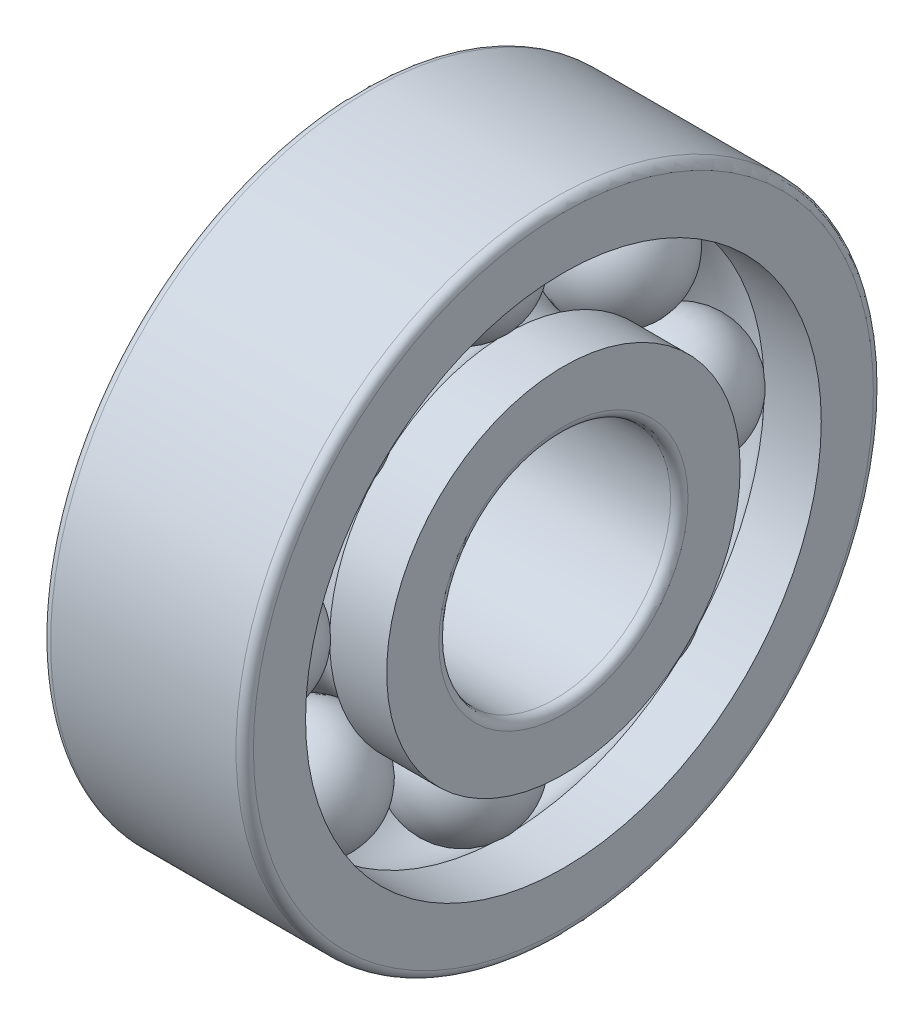
SolidWorks part; units mm, degrees
ref_plane "Plane1" through (0, 0, 0) normal (0, 0, 1) x (1, 0, 0)
ref_plane "Plane2" through (0, 0, 0) normal (0, 1, 0) x (1, 0, 0)
ref_plane "Plane3" through (0, 0, 0) normal (1, 0, 0) x (0, 0, -1)
sketch "Clipboard" plane through (0, 0, 0) normal (0, 0, 1) x (1, 0, 0)
  line L0 (-10, 0) -> (10, 0) construction
  line L1 (0, 0) -> (22.1431, -3.112)
  line L2 (0, 0) -> (7.427, 1.0438)
  line L3 (0, 0) -> (22.1431, -3.112)
  line L4 (0, 0) -> (-22.3573, -0.3902)
  dimension "BallCLRad" = 7.5
sketch "CagSpiSke" plane through (0, 0, 0) normal (0, 0, 1) x (1, 0, 0)
  line L0 (0.21, 7.15) -> (0.21, 7.85)
  line L1 (0.21, 7.85) -> (-0.21, 7.85)
  line L2 (-0.21, 7.85) -> (-0.21, 7.15)
  line L3 (-0.21, 7.15) -> (0.21, 7.15)
  line L4 (-20.6375, 0) -> (20.6375, 0) construction
  line L5 (0, 0) -> (0, 23.7692) construction
  dimension "OD" = 15.7
  dimension "ID" = 14.3
revolve "CageSpine" add sketch "CagSpiSke" angle 0.001 about L4 reverse direction yes
ref_axis "Axis1" through (-50, 0, 0) along (1, 0, 0)
sketch "CagBalSke" plane through (0, 0, 0) normal (0, 0, 1) x (1, 0, 0)
  line L0 (-2.31, 7.5) -> (2.31, 7.5)
  line L1 (-1.905, 7.5) -> (1.905, 7.5) construction
  line L2 (-10, 0) -> (10, 0) construction
  line L3 (0, 0) -> (0, 24) construction
  arc A0 (2.31, 7.5) -> (-2.31, 7.5) centre (0, 7.5) cw
  dimension "BallCLRad" = 7.5
revolve "CageBall" [suppressed] add sketch "CagBalSke" angle 360 about L1 reverse direction yes
pattern_circular "CageBalls" [suppressed] count 8 every 45 about axis through (-50, 0, 0) along (1, 0, 0)
sketch "CagTrmODSke" plane through (0, 0, 0) normal (0, 0, 1) x (1, 0, 0)
  line L0 (2.311, 7.85) -> (2.311, 9.811)
  line L1 (2.311, 9.811) -> (-2.311, 9.811)
  line L2 (-2.311, 9.811) -> (-2.311, 7.85)
  line L3 (-2.311, 7.85) -> (2.311, 7.85)
  line L4 (-20.6375, 0) -> (20.6375, 0) construction
  line L5 (0, 0) -> (0, 25) construction
  dimension "Width" = 4.622
  dimension "ID" = 15.7
  dimension "OD" = 19.622
revolve "CageTrimOD" [suppressed] cut sketch "CagTrmODSke" angle 360 about L4 reverse direction yes
sketch "CagTrmIDSke" plane through (0, 0, 0) normal (0, 0, 1) x (1, 0, 0)
  line L0 (2.311, 5.191) -> (2.311, 7.15)
  line L1 (2.311, 7.15) -> (-2.311, 7.15)
  line L2 (-2.311, 7.15) -> (-2.311, 5.191)
  line L3 (-2.311, 5.191) -> (2.311, 5.191)
  line L4 (-20.6375, 0) -> (20.6375, 0) construction
  line L5 (0, 0) -> (0, 25) construction
  dimension "Width" = 4.622
  dimension "ID" = 10.382
  dimension "OD" = 14.3
revolve "CageTrimID" [suppressed] cut sketch "CagTrmIDSke" angle 360 about L4 reverse direction yes
sketch "BalSimSke" plane through (0, 0, 0) normal (0, 0, 1) x (1, 0, 0)
  line L0 (-10, 0) -> (10, 0) construction
  line L1 (-10, 7.5) -> (10, 7.5) construction
  line L2 (0, 0) -> (0, 23) construction
  circle A0 centre (0, 7.5) radius 2.1
  dimension "BallCLRad" = 7.5
  dimension "Ball_diameter" = 4.2
revolve "BallsSimplified" [suppressed] add sketch "BalSimSke" angle 360 about L0
sketch "BalDetSke" plane through (0, 0, 0) normal (0, 0, 1) x (1, 0, 0)
  line L0 (-2.1, 7.5) -> (2.1, 7.5)
  line L1 (-1.905, 7.5) -> (1.905, 7.5) construction
  line L2 (0, 0) -> (0, 25) construction
  arc A0 (2.1, 7.5) -> (-2.1, 7.5) centre (0, 7.5) cw
  dimension "BallCLRad" = 7.5
  dimension "Ball_diameter" = 4.2
revolve "BallDetailed" add sketch "BalDetSke" angle 360 about L1 reverse direction yes
sketch "InnRacSke" plane through (0, 0, 0) normal (0, 0, 1) x (1, 0, 0)
  line L0 (-1.5315, 6.1) -> (-3.5, 6.1)
  line L1 (-3.5, 6.1) -> (-3.5, 4.3)
  line L2 (-3.2, 4) -> (3.2, 4)
  line L3 (3.5, 4.3) -> (3.5, 6.1)
  line L4 (3.5, 6.1) -> (1.5315, 6.1)
  line L5 (-20.6375, 0) -> (20.6375, 0) construction
  line L6 (0, 0) -> (0, 30) construction
  arc A0 (-3.5, 4.3) -> (-3.2, 4) centre (-3.2, 4.3) ccw
  arc A1 (3.2, 4) -> (3.5, 4.3) centre (3.2, 4.3) ccw
  arc A2 (1.5315, 6.1) -> (-1.5315, 6.1) centre (0, 7.5) cw
  dimension "BallCLRad" = 7.5
  dimension "Fillet_radius" = 0.3
  dimension "Ball_diameter" = 4.15
  dimension "ID" = 8
  dimension "OD" = 12.2
  dimension "Width" = 7
revolve "InnerRace" add sketch "InnRacSke" angle 360 about L5 reverse direction yes
sketch "OutRacSke" plane through (0, 0, 0) normal (0, 0, 1) x (1, 0, 0)
  line L0 (-1.5315, 8.9) -> (-3.5, 8.9)
  line L1 (-3.5, 8.9) -> (-3.5, 10.7)
  line L2 (-3.2, 11) -> (3.2, 11)
  line L3 (3.5, 10.7) -> (3.5, 8.9)
  line L4 (3.5, 8.9) -> (1.5315, 8.9)
  line L5 (-20.6375, 0) -> (20.6375, 0) construction
  line L6 (0, 0) -> (0, 30) construction
  arc A0 (-3.5, 10.7) -> (-3.2, 11) centre (-3.2, 10.7) cw
  arc A1 (3.2, 11) -> (3.5, 10.7) centre (3.2, 10.7) cw
  arc A2 (1.5315, 8.9) -> (-1.5315, 8.9) centre (0, 7.5) ccw
  dimension "BallCLRad" = 7.5
  dimension "Fillet_radius" = 0.3
  dimension "Ball_diameter" = 4.15
  dimension "Width" = 7
revolve "OuterRace" add sketch "OutRacSke" angle 360 about L5 reverse direction yes
pattern_circular "BallsDetailed" count 8 every 45 about axis through (-50, 0, 0) along (1, 0, 0) of "BallDetailed"
equation "\"BallCLRad@Clipboard\" = ( \"OD@OutRacSke\" + \"ID@InnRacSke\" ) / 4"
equation "\"BallCLRad@BalSimSke\" = \"BallCLRad@Clipboard\""
equation "\"BallCLRad@BalDetSke\" = \"BallCLRad@Clipboard\""
equation "\"BallCLRad@InnRacSke\" = \"BallCLRad@Clipboard\""
equation "\"BallCLRad@OutRacSke\" = \"BallCLRad@Clipboard\""
equation "\"Ball_diameter@InnRacSke\" = \"Ball_diameter@BalDetSke\" - 0.05"
equation "\"Ball_diameter@OutRacSke\" = \"Ball_diameter@BalDetSke\" - 0.05"
equation "\"Ball_diameter@BalSimSke\" = \"Ball_diameter@BalDetSke\""
equation "\"Width@OutRacSke\" = \"Width@InnRacSke\""
equation "\"Fillet_radius@OutRacSke\" = \"Fillet_radius@InnRacSke\""
equation "\"Max_count@Clipboard\" = int( 3.14159265 / atn(( \"Ball_diameter@BalDetSke\" / 2) / sqr( \"BallCLRad@Clipboard\"  *  \"BallCLRad@Clipboard\" - ( \"Ball_diameter@BalDetSke\" / 2) *  ( \"Ball_diameter@BalDetSke\" / 2))))"
equation "\"Max_count@Clipboard\" = ((sgn( \"Max_count@Clipboard\" - \"Count@Clipboard\" )-1)*( \"Max_count@Clipboard\" - \"Count@Clipboard\" ))/-2+ \"Count@Clipboard\""
equation "\"Count@BallsDetailed\" = int( \"Show_count@Clipboard\" ) "
equation "\"Count@BallsDetailed\" = ((sgn( \"Count@BallsDetailed\" - \"Max_count@Clipboard\" )-1)*( \"Count@BallsDetailed\" - \"Max_count@Clipboard\" ))/-2+ \"Max_count@Clipboard\""
equation "\"Count@BallsDetailed\" = ((sgn( \"Count@BallsDetailed\" - \"Min_count@Clipboard\" )+1)*( \"Count@BallsDetailed\" - \"Min_count@Clipboard\"))/2 +\"Min_count@Clipboard\""
equation "\"Angle@BallsDetailed\" = 360.0 / \"Max_count@Clipboard\""
equation "\"BallCLRad@CagBalSke\" = \"BallCLRad@Clipboard\""
equation "\"Count@CageBalls\" = \"Count@BallsDetailed\""
equation "\"Angle@CageBalls\" = \"Angle@BallsDetailed\""
equation "\"Angle@CageSpine\" =  \"Angle@CageBalls\" * ( \"Count@CageBalls\" -1 + int( \"Count@CageBalls\" / \"Max_count@Clipboard\" ) )  + 0.001 -  int( \"Count@CageBalls\" / \"Max_count@Clipboard\" ) * 0.001"
equation "\"Angle@CageSpine\" =  \"Angle@CageSpine\" * int( \"Min_count@Clipboard\" / 2) + int(1 / \"Min_count@Clipboard\")  * 0.001"
equation "\"CageWallOD@CagBalSke\" =  \"Ball_diameter@BalDetSke\" * 1.1"
equation "\"Thickness@CagSpiSke\" =  \"Ball_diameter@BalDetSke\" * 0.1"
equation "\"OD@CagTrmODSke\" = \"BallCLRad@Clipboard\" * 2 + \"CageWallOD@CagBalSke\" + 0.002"
equation "\"ID@CagTrmODSke\" = \"BallCLRad@Clipboard\" * 2 + \"Ball_diameter@BalDetSke\" / 6"
equation "\"OD@CagTrmIDSke\" = \"BallCLRad@Clipboard\" * 2 - \"Ball_diameter@BalDetSke\" / 6"
equation "\"ID@CagTrmIDSke\" = \"BallCLRad@Clipboard\" * 2 - \"CageWallOD@CagBalSke\" + 0.002"
equation "\"OD@CagSpiSke\" = \"ID@CagTrmODSke\""
equation "\"ID@CagSpiSke\" = \"OD@CagTrmIDSke\""
equation "\"Width@CagTrmODSke\" = \"CageWallOD@CagBalSke\" + 0.002"
equation "\"Width@CagTrmIDSke\" = \"CageWallOD@CagBalSke\" + 0.002"
